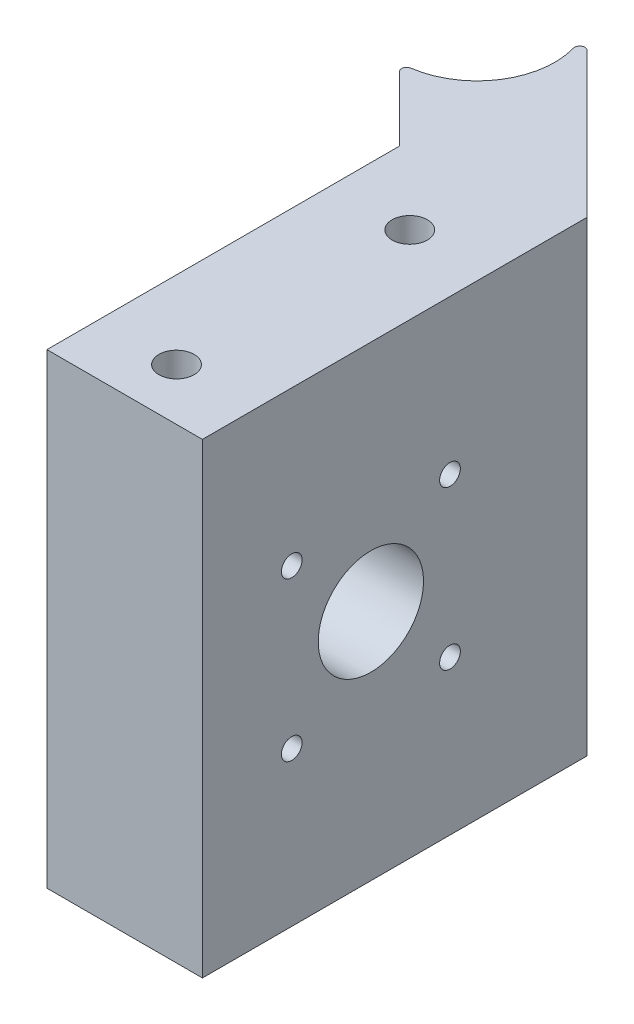
SolidWorks part; units mm, degrees
ref_plane "Front Plane" through (0, 0, 0) normal (0, 0, 1) x (1, 0, 0)
ref_plane "Top Plane" through (0, 0, 0) normal (0, 1, 0) x (1, 0, 0)
ref_plane "Right Plane" through (0, 0, 0) normal (1, 0, 0) x (0, 0, -1)
sketch "Sketch1" plane through (0, 0, 0) normal (0, 1, 0) x (1, 0, 0)
  line L0 (-14.5, 51) -> (7.5, 51) construction
  line L1 (7.5, 51) -> (7.5, 32.1066) construction
  line L2 (7.5, -5) -> (-7.5, -5)
  line L3 (-7.5, -5) -> (-7.5, 29)
  line L4 (-7.5, 36) -> (-14.5, 36) construction
  line L5 (0, 0) -> (0, -5) construction
  line L6 (-14.5, 36) -> (-7.5, 29)
  line L7 (-9.1967, 48.8033) -> (7.5, 32.1066)
  line L8 (-7.5, 29) -> (-7.5, 36) construction
  line L9 (7.5, 32.1066) -> (7.5, -5)
  circle A0 centre (0, 22.5) radius 1.7
  circle A1 centre (0, 0) radius 1.7
  arc A2 (-14.5, 36) -> (-9.1967, 48.8033) centre (-14.5, 43.5) ccw
  arc A3 (-9.1967, 48.8033) -> (-14.5, 51) centre (-14.5, 43.5) ccw construction
  dimension "D2" = 3.4
  dimension "D3" = 15
  dimension "D1" = 22.5
  dimension "D4" = 14.5
  dimension "D5" = 21
  dimension "D6" = 15
  dimension "D7" = 5
  dimension "D8" = 45
extrude "Boss-Extrude1" add sketch "Sketch1" along normal blind 45 contours A2 L6 L3 L2 L9 L7 A1 A0 region at (-0.873, 0, -18.4765)
sketch "Sketch2" plane through (7.5, 0, 0) normal (1, 0, 0) x (0, 0, -1)
  line L0 (3.617, 30.133) -> (18.883, 14.867) construction
  line L1 (3.617, 30.133) -> (18.883, 30.133) construction
  line L2 (3.617, 30.133) -> (3.617, 14.867) construction
  line L3 (3.617, 14.867) -> (18.883, 14.867) construction
  line L4 (18.883, 30.133) -> (18.883, 14.867) construction
  line L5 (-5, 22.5) -> (11.25, 22.5) construction
  line L6 (-5, 45) -> (-5, 0) construction
  circle A0 centre (11.25, 22.5) radius 5.08
  circle A1 centre (3.617, 30.133) radius 1
  circle A2 centre (18.883, 30.133) radius 1
  circle A3 centre (18.883, 14.867) radius 1
  circle A4 centre (3.617, 14.867) radius 1
  dimension "D1" = 10.16
  dimension "D3" = 2
  dimension "D2" = 15.266
  dimension "D4" = 16.25
extrude "Cut-Extrude1" cut sketch "Sketch2" against normal up to next
fillet "Fillet1" radius 0.5 2 edges at (-9.1967, 22.5, -48.8033) (-14.5, 22.5, -36)
ref_plane "Plane1" through (0, 22.5, 0) normal (0, 1, 0) x (1, 0, 0)
sketch "Sketch3" plane through (0, 22.5, 0) normal (0, 1, 0) x (1, 0, 0)
  line L0 (-8.136, 37.136) -> (-2.8327, 42.4393)
  line L1 (-6.4581, 46.0647) -> (7.5, 32.1066) construction
  line L2 (-1.7721, 41.3787) -> (-7.0754, 36.0754)
  line L3 (-13.7263, 35.2263) -> (-7.5, 29) construction
  line L4 (-13.1083, 34.6083) -> (-11.842, 33.342)
  line L5 (-2.8327, 42.4393) -> (-1.7721, 41.3787)
  arc A0 (-13.1083, 34.6083) -> (-8.136, 37.136) centre (-14.5, 43.5) ccw
  arc A1 (-7.0754, 36.0754) -> (-11.842, 33.342) centre (-14.5, 43.5) cw
  dimension "D1" = 18
  dimension "D2" = 1.5
extrude "Cut-Extrude2" cut sketch "Sketch3" against normal mid plane 4
extrude "Cut-Extrude3" cut sketch "Sketch3<2>" against normal mid plane 4 from offset 17
sketch "Sketch3<2>" plane through (0, 22.5, 0) normal (0, 1, 0) x (1, 0, 0) same geometry as "Sketch3"
mirror "Mirror1" about plane through (0, 22.5, 0) normal (0, 1, 0) of "Cut-Extrude3"
